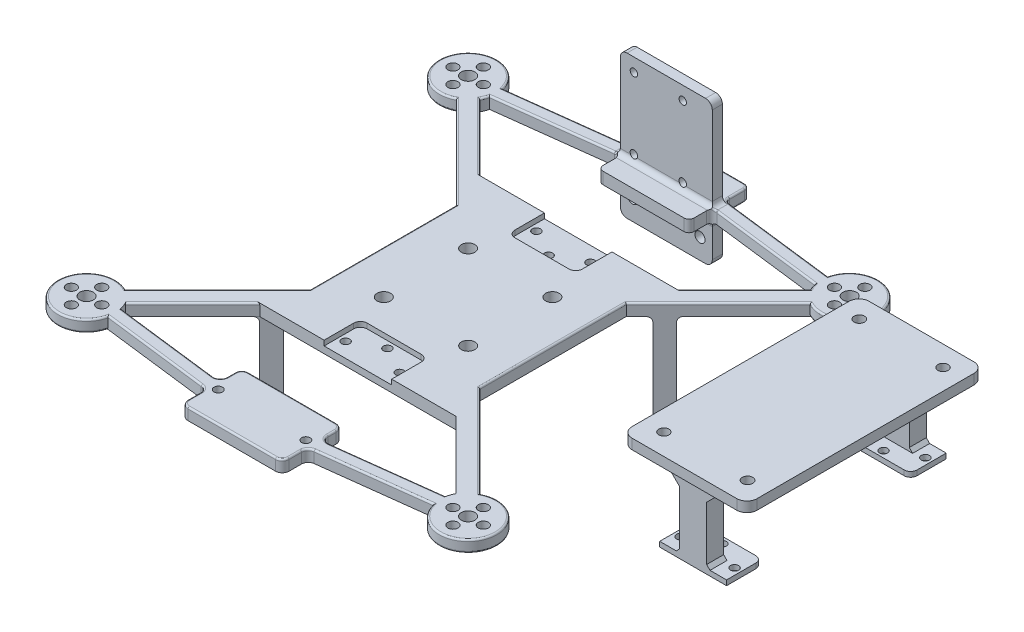
SolidWorks part; units mm, degrees
ref_plane "Front Plane" through (0, 0, 0) normal (0, 0, 1) x (1, 0, 0)
ref_plane "Top Plane" through (0, 0, 0) normal (0, 1, 0) x (1, 0, 0)
ref_plane "Right Plane" through (0, 0, 0) normal (1, 0, 0) x (0, 0, -1)
sketch "Sketch1" plane through (0, 0, 0) normal (0, 1, 0) x (1, 0, 0)
  line L10 (25.2228, 21.7178) -> (52.5194, 49.0143)
  line L11 (29.1718, 32.6991) -> (49.0032, 52.5305)
  line L14 (25.2228, -21.7245) -> (52.5163, -49.018)
  line L15 (29.1386, -32.6991) -> (48.9964, -52.5569)
  line L19 (-25.2228, 21.7178) -> (-52.5879, 49.0829)
  line L20 (-29.1386, -32.6991) -> (-49.0885, -52.649)
  line L22 (-25.2228, -21.7245) -> (-52.6084, -49.1101)
  line L33 (-25.2228, -21.7245) -> (-25.2228, 21.7178)
  line L34 (-16.8093, -62.3977) -> (-48.3224, -58.53)
  line L37 (-8.5504, -52.1195) -> (8.5504, -52.1195)
  line L41 (-17.2966, -58.4661) -> (-48.3352, -54.6566)
  line L42 (25.2228, -21.7245) -> (25.2228, 21.7178)
  line L43 (-48.2996, 54.661) -> (-15.2357, 58.719)
  line L44 (17.1959, -58.4785) -> (48.2122, -54.6717)
  line L45 (16.7086, -62.4101) -> (48.2307, -58.5412)
  line L46 (-29.1718, 32.6991) -> (29.1718, 32.6991)
  line L47 (-29.1386, -32.6991) -> (29.1386, -32.6991)
  line L48 (14.7695, 62.6481) -> (48.2209, 58.5424)
  line L49 (15.135, 58.7314) -> (48.2038, 54.6727)
  line L50 (-13.553, 57.2302) -> (-13.553, 53.6195)
  line L51 (-13.553, 64.1245) -> (-13.553, 68.595)
  line L52 (13.4522, 57.2426) -> (13.4522, 53.6195)
  line L53 (-12.053, 52.1195) -> (11.9522, 52.1195)
  line L54 (-15.053, -56.481) -> (-15.053, -54.1195)
  line L55 (-49.0752, 52.6025) -> (-29.1718, 32.6991)
  line L56 (14.9522, -64.3952) -> (14.9522, -68.095)
  line L57 (-14.8702, 62.6357) -> (-48.3224, 58.53)
  line L58 (12.9522, -70.095) -> (-13.053, -70.095)
  line L64 (-12.053, 70.095) -> (11.9522, 70.095)
  line L65 (13.4522, 68.595) -> (13.4522, 64.1369)
  line L66 (-15.053, -68.095) -> (-15.053, -64.3828)
  line L67 (14.9522, -56.4934) -> (14.9522, -54.1195)
  line L68 (12.9522, -52.1195) -> (-13.053, -52.1195)
  line L69 (14.9522, -52.1195) -> (14.9522, -58.7538)
  arc A0 (-52.6084, -49.1101) -> (-48.3224, -58.53) centre (-56.6207, -56.6207) ccw
  arc A1 (52.5194, 49.0143) -> (48.2209, 58.5424) centre (56.5594, 56.5706) ccw
  arc A2 (-49.0752, 52.6025) -> (-48.2996, 54.661) centre (-56.6207, 56.6207) ccw
  arc A3 (48.9964, -52.5569) -> (48.2122, -54.6717) centre (56.5667, -56.5667) ccw
  arc A8 (-48.3352, -54.6566) -> (-49.0885, -52.649) centre (-56.6207, -56.6207) ccw
  arc A9 (48.2307, -58.5412) -> (52.5163, -49.018) centre (56.5667, -56.5667) ccw
  arc A11 (13.4522, 64.1369) -> (14.7695, 62.6481) centre (14.9522, 64.1369) ccw
  arc A12 (15.135, 58.7314) -> (13.4522, 57.2426) centre (14.9522, 57.2426) ccw
  arc A13 (-13.553, 64.1245) -> (-14.8702, 62.6357) centre (-15.053, 64.1245) cw
  arc A14 (-49.0752, 52.6025) -> (-48.2996, 54.661) centre (-56.6207, 56.6207) ccw
  arc A15 (48.2038, 54.6727) -> (49.0032, 52.5305) centre (56.5594, 56.5706) ccw
  arc A16 (-48.2888, 58.5341) -> (-52.5879, 49.0829) centre (-56.6207, 56.6207) ccw
  arc A17 (14.9522, -56.4934) -> (17.1959, -58.4785) centre (16.9522, -56.4934) ccw
  arc A20 (16.7086, -62.4101) -> (14.9522, -64.3952) centre (16.9522, -64.3952) ccw
  arc A21 (-15.2357, 58.719) -> (-13.553, 57.2302) centre (-15.053, 57.2302) cw
  arc A22 (-13.553, 53.6195) -> (-12.053, 52.1195) centre (-12.053, 53.6195) ccw
  arc A23 (11.9522, 52.1195) -> (13.4522, 53.6195) centre (11.9522, 53.6195) ccw
  arc A24 (11.9522, 70.095) -> (13.4522, 68.595) centre (11.9522, 68.595) cw
  arc A25 (-12.053, 70.095) -> (-13.553, 68.595) centre (-12.053, 68.595) ccw
  arc A26 (-15.053, -56.481) -> (-17.2966, -58.4661) centre (-17.053, -56.481) cw
  arc A27 (-15.053, -64.3828) -> (-16.8093, -62.3977) centre (-17.053, -64.3828) ccw
  arc A28 (-13.053, -70.095) -> (-15.053, -68.095) centre (-13.053, -68.095) cw
  arc A29 (12.9522, -70.095) -> (14.9522, -68.095) centre (12.9522, -68.095) ccw
  arc A30 (14.9522, -54.1195) -> (12.9522, -52.1195) centre (12.9522, -54.1195) ccw
  arc A31 (-15.053, -54.1195) -> (-13.053, -52.1195) centre (-13.053, -54.1195) cw
  point P10 (0, 0)
  point P34 (14.9522, -62.6256)
  point P37 (-15.053, -58.7415)
  point P44 (-28.9553, -58.9711)
  point P57 (13.4522, 58.9379)
  dimension "D1" = 2
  dimension "D2" = 1.5
extrude "Boss-Extrude1" add sketch "Sketch1" along normal blind 3.5 contours A16 L19 L33 L22 A0 L34 L45 A9 L14 L42 L10 A1 L48 L50 L57 L49 A15 L11 L46 L55 A2 L43 A13 L41 A8 L20 L47 L15 A3 L44 L37 region at (0.0088, 0, 0.3906)
sketch "Sketch2" plane through (0, 3.5, 0) normal (0, 1, 0) x (1, 0, 0)
  circle A0 centre (-56.6207, 56.6207) radius 2.003
  circle A1 centre (56.6207, 56.6207) radius 2.003
  circle A2 centre (56.6207, -56.6274) radius 2.003
  circle A3 centre (-56.6207, -56.6274) radius 2.003
  circle A6 centre (56.6207, 61.1356) radius 1.498
  circle A7 centre (61.1356, 56.6207) radius 1.495
  circle A8 centre (56.6207, 52.1058) radius 1.5029
  circle A9 centre (52.1058, 56.6207) radius 1.5021
  circle A10 centre (-56.6207, 61.1356) radius 1.498
  circle A11 centre (-52.1058, 56.6207) radius 1.5021
  circle A12 centre (-56.6207, 52.1058) radius 1.5029
  circle A13 centre (-61.1356, 56.6207) radius 1.495
  circle A14 centre (56.6207, -61.1356) radius 1.498
  circle A15 centre (52.1058, -56.6207) radius 1.5021
  circle A16 centre (56.6207, -52.1058) radius 1.5029
  circle A17 centre (61.1356, -56.6207) radius 1.495
  circle A18 centre (-56.6207, -61.1356) radius 1.498
  circle A19 centre (-52.1058, -56.6207) radius 1.5021
  circle A20 centre (-61.1356, -56.6207) radius 1.495
  circle A21 centre (-56.6207, -52.1058) radius 1.5029
  circle A22 centre (-12.2493, 12.2453) radius 1.9968
  circle A23 centre (-12.2493, -12.7715) radius 1.9976
  circle A24 centre (12.7793, -12.7715) radius 1.9993
  circle A25 centre (12.7793, 12.2453) radius 2.0015
extrude "Cut-Extrude1" cut sketch "Sketch2" against normal through all
sketch "Sketch3" plane through (0, 0, 0) normal (0, -1, 0) x (1, 0, 0)
  line L1 (-25.2228, -21.7178) -> (-52.5879, -49.0829) construction
  line L3 (-29.1718, -32.6991) -> (-32.6879, -29.1829)
  line L4 (-29.1718, -32.6991) -> (-25.6556, -29.1829)
  line L5 (-32.6879, -29.1829) -> (-29.1718, -25.6667)
  line L6 (-25.6556, -29.1829) -> (-29.1718, -25.6667)
  line L7 (32.6879, -29.1829) -> (29.1718, -25.6667)
  line L8 (29.1718, -32.6991) -> (32.6879, -29.1829)
  line L9 (29.1718, -32.6991) -> (25.6556, -29.1829)
  line L10 (25.6556, -29.1829) -> (29.1718, -25.6667)
  line L13 (32.6879, 29.1896) -> (29.1718, 25.6735)
  line L14 (29.1718, 32.7058) -> (32.6879, 29.1896)
  line L15 (25.6556, 29.1896) -> (29.1718, 25.6735)
  line L16 (29.1718, 32.7058) -> (25.6556, 29.1896)
  line L17 (-32.6879, 29.1896) -> (-29.1718, 25.6735)
  line L18 (-29.1718, 32.7058) -> (-25.6556, 29.1896)
  line L19 (-29.1718, 32.7058) -> (-32.6879, 29.1896)
  line L20 (-25.6556, 29.1896) -> (-29.1718, 25.6735)
extrude "Boss-Extrude2" add sketch "Sketch3" along normal blind 30 and the other way blind 2.5
fillet "Fillet1" radius 1.5 8 edges at (30.9299, 0, -30.941) (-27.4137, 0, 27.4316) (30.9299, 0, 30.9477) (-27.4137, 0, -27.4248) (-30.9299, 0, 30.9477) (27.4137, 0, 27.4316) (-30.9299, 0, -30.941) (27.4137, 0, -27.4248)
sketch "Sketch4" plane through (0, 3.5, 0) normal (0, 1, 0) x (1, 0, 0)
  line L8 (-13.885, 59.0576) -> (13.4118, 59.0576)
  line L9 (-13.885, 59.0576) -> (-13.885, 62.0613)
  line L10 (-13.885, 62.0613) -> (13.4118, 62.0613)
  line L11 (13.4118, 59.0576) -> (13.4118, 62.0613)
extrude "Boss-Extrude3" add sketch "Sketch4" along normal blind 27 and the other way blind 15.5
fillet "Fillet2" radius 1.5 6 edges at (-0.2366, 0, -59.0576) (13.4118, 3.5, -60.5595) (-0.2366, 3.5, -59.0576) (-13.885, 3.5, -60.5595) (-13.885, 0, -60.5595) (13.4118, 0, -60.5595)
fillet "Fillet3" radius 2 4 edges at (13.4118, -12, -60.5595) (-13.885, -12, -60.5595) (13.4118, 30.5, -60.5595) (-13.885, 30.5, -60.5595)
sketch "Sketch5" plane through (0, 0, -62.0613) normal (0, 0, -1) x (-1, 0, 0)
  circle A3 centre (9.8595, 5.5028) radius 1.1031
  circle A4 centre (-4.6441, 5.5028) radius 1.0992
  circle A5 centre (9.8595, 26.5151) radius 1.0963
  circle A6 centre (-4.6441, 26.5151) radius 1.0933
  circle A7 centre (-9.7641, -6) radius 1.4993
  circle A8 centre (10.2386, -6) radius 1.4966
extrude "Cut-Extrude2" cut sketch "Sketch5" against normal up to next
fillet "Fillet6" radius 0.5 61 edges at (-14.7161, 3.6574, -58.6919) (-15.3102, 3.5019, -58.7099) (14.5178, 3.5527, -58.6783) (15.0236, 3.5, -58.7409) (32.7041, 3.5, 56.5751) (-0.0504, 3.5, 52.1195) (32.4696, 3.5, 60.4757) (-31.5795, 0, -60.5849) (-13.9296, 0, -63.1306) (-13.553, 0, -66.3598) (-13.1136, 0, -69.6557) (31.4952, 0, -60.5953) (13.8288, 0, -63.1429) (13.4522, 0, -66.366) (13.0129, 0, -69.6557) (-31.5795, 3.5, -60.5849) (-13.9296, 3.5, -63.1306) (-13.553, 3.5, -66.3598) (-13.1136, 3.5, -69.6557) (-0.0504, 3.5, -70.095) (13.0129, 3.5, -69.6557) (13.4522, 3.5, -66.366) (13.8288, 3.5, -63.1429) (-31.8423, 3.5, -56.6808) (-48.6209, 3.5, -53.6067) (31.6694, 3.5, -56.7021) (48.5317, 3.5, -53.5748) (39.0875, 3.5, -42.6148) (-39.1235, 3.5, -42.6508) (38.8711, 3.5, -35.366) (25.2228, 3.5, 0.0034) (38.8696, 3.5, 35.3713) (64.3788, 0, 60.0823) (64.3788, 3.5, 60.0823) (-39.1136, 3.5, 42.674) (-32.8159, 3.5, 56.5614) (-32.5659, 3.5, 60.4638) (-64.3713, 0, 60.1472) (-64.3713, 3.5, 60.1472) (-38.9156, 3.5, 35.4173) (-25.2228, 3.5, 0.0034) (-38.9054, 3.5, -35.4003) (-64.4022, 3.5, -60.1603) (-64.4022, 0, -60.1603) (64.3699, 0, -60.0942) (-0.0504, 0, -70.095) (31.4952, 3.5, -60.5953) (64.3699, 3.5, -60.0942) (15.627, 3.5, 57.9912) (14.9522, 3.5, 55.3064) (14.3664, 3.5, 52.7053) (-14.4672, 3.5, 52.7053) (-15.053, 3.5, 55.3003) (-15.7277, 3.5, 57.9789) (15.4544, 3.5, 63.0699) (14.9522, 3.5, 66.2451) (14.3664, 3.5, 69.5092) (-0.0504, 3.5, 70.095) (-14.4672, 3.5, 69.5092) (-15.053, 3.5, 66.2389) (-15.5551, 3.5, 63.0575)
sketch "Sketch6" plane through (0, 3.5, 0) normal (0, 1, 0) x (1, 0, 0)
  line L4 (10.0048, -23.9249) -> (10.0048, -32.6991)
  line L5 (-29.8789, 32.6991) -> (29.8789, 32.6991) construction
  line L6 (10.0048, -32.6991) -> (-10.0395, -32.6991)
  line L7 (-10.0395, -32.6991) -> (-10.0395, -23.9249)
  line L8 (-8.0395, -21.9249) -> (8.0048, -21.9249)
  line L10 (-8.0395, 21.9249) -> (8.0048, 21.9249)
  line L11 (10.0048, 23.9249) -> (10.0048, 32.6991)
  line L12 (10.0048, 32.6991) -> (-10.0395, 32.6991)
  line L13 (-10.0395, 32.6991) -> (-10.0395, 23.9249)
  arc A0 (8.0048, 21.9249) -> (10.0048, 23.9249) centre (8.0048, 23.9249) ccw
  arc A1 (-10.0395, 23.9249) -> (-8.0395, 21.9249) centre (-8.0395, 23.9249) ccw
  arc A2 (8.0048, -21.9249) -> (10.0048, -23.9249) centre (8.0048, -23.9249) cw
  arc A3 (-10.0395, -23.9249) -> (-8.0395, -21.9249) centre (-8.0395, -23.9249) cw
  dimension "D1" = 2
extrude "Cut-Extrude3" cut sketch "Sketch6" against normal blind 1.5
sketch "Sketch7" plane through (0, 2, 0) normal (0, 1, 0) x (1, 0, 0)
  circle A0 centre (-8.0479, 28.312) radius 1.205
  circle A1 centre (-0.0173, 23.9294) radius 1.1998
  circle A2 centre (8.0011, 28.312) radius 1.205
  circle A3 centre (8.0011, -28.312) radius 1.205
  circle A4 centre (-0.0173, -23.9294) radius 1.1998
  circle A5 centre (-8.0479, -28.312) radius 1.205
extrude "Cut-Extrude5" cut sketch "Sketch7" against normal through all
sketch "Sketch10" plane through (0, 3.5, 0) normal (0, 1, 0) x (1, 0, 0)
  circle A0 centre (-13.053, -61.1073) radius 1.2524
  circle A1 centre (12.9522, -61.1073) radius 1.2475
extrude "Cut-Extrude6" cut sketch "Sketch10" against normal through all
sketch "Sketch11" plane through (0, 0, 0) normal (0, 1, 0) x (1, 0, 0)
  line L4 (89.4618, 32.5991) -> (89.4618, 23.9249)
  line L5 (107.4062, 22.0249) -> (91.3618, 22.0249)
  line L6 (109.3062, 32.5991) -> (109.3062, 23.9249)
  line L7 (89.4618, 32.5991) -> (109.3062, 32.5991)
  line L10 (109.3062, -32.5991) -> (109.3062, -23.9249)
  line L11 (107.4062, -22.0249) -> (91.3618, -22.0249)
  line L12 (89.4618, -32.5991) -> (109.3062, -32.5991)
  line L13 (89.4618, -32.5991) -> (89.4618, -23.9249)
  arc A2 (91.3618, 22.0249) -> (89.4618, 23.9249) centre (91.3618, 23.9249) cw
  arc A3 (107.4062, 22.0249) -> (109.3062, 23.9249) centre (107.4062, 23.9249) ccw
  arc A4 (107.4062, -22.0249) -> (109.3062, -23.9249) centre (107.4062, -23.9249) cw
  arc A5 (91.3618, -22.0249) -> (89.4618, -23.9249) centre (91.3618, -23.9249) ccw
extrude "Boss-Extrude4" add sketch "Sketch11" along normal blind 1.5 separate body
sketch "Sketch12" plane through (0, 1.5, 0) normal (0, 1, 0) x (1, 0, 0)
  circle A0 centre (91.3535, 28.3053) radius 1.205
  circle A1 centre (99.384, 23.9228) radius 1.1998
  circle A2 centre (107.4025, 28.3053) radius 1.205
  circle A3 centre (107.4025, -28.3186) radius 1.205
  circle A4 centre (99.384, -23.9361) radius 1.1998
  circle A5 centre (91.3535, -28.3186) radius 1.205
extrude "Cut-Extrude7" cut sketch "Sketch12" against normal through all
sketch "Sketch13" plane through (0, 1.5, 0) normal (0, 1, 0) x (1, 0, 0)
  line L2 (109.3062, 32.5991) -> (89.4618, 32.5991) construction
  line L7 (95.3874, 32.5991) -> (95.3874, 27.5424)
  line L8 (95.3874, 27.5424) -> (103.3936, 27.5424)
  line L9 (103.3936, 32.5991) -> (103.3936, 27.5424)
  line L15 (103.3936, -32.5991) -> (103.3936, -27.5424)
  line L16 (95.3874, -32.5991) -> (95.3874, -27.5424)
  line L17 (95.3874, -27.5424) -> (103.3936, -27.5424)
  line L18 (95.3874, -32.5991) -> (103.3936, -32.5991)
  line L19 (95.3874, 32.5991) -> (103.3936, 32.5991)
extrude "Boss-Extrude5" add sketch "Sketch13" along normal blind 23.5 and the other way blind 1.253
sketch "Sketch14" plane through (0, 25, 0) normal (0, 1, 0) x (1, 0, 0)
  line L0 (80.8723, 35.1637) -> (80.8723, -35.1882)
  line L3 (80.8723, 35.1637) -> (117.9365, 35.1637)
  line L4 (80.8723, -35.1882) -> (117.9365, -35.1882)
  line L5 (117.9365, -35.1882) -> (117.9365, 35.1637)
extrude "Boss-Extrude6" add sketch "Sketch14" along normal blind 1.5 and the other way blind 1.5
fillet "Fillet10" radius 3 4 edges at (80.8723, 25, -35.1637) (117.9365, 25, -35.1637) (80.8723, 25, 35.1882) (117.9365, 25, 35.1882)
sketch "Sketch15" plane through (0, 26.5, 0) normal (0, 1, 0) x (1, 0, 0)
  circle A4 centre (86.9844, 29.1301) radius 1.546
  circle A5 centre (111.8244, 29.1301) radius 1.5226
  circle A6 centre (86.9844, -28.8874) radius 1.5055
  circle A7 centre (111.8244, -28.8874) radius 1.5537
extrude "Cut-Extrude8" cut sketch "Sketch15" against normal up to next (3 mm away)
chamfer "Chamfer2" distance 1 angle 45 4 edges at (95.3874, 1.5, 30.0707) (95.3874, 1.5, -30.0707) (103.3936, 1.5, -30.0707) (103.3936, 1.5, 30.0707)
chamfer "Chamfer3" distance 5 angle 45 4 edges at (103.3936, 23.5, 30.0707) (95.3874, 23.5, 30.0707) (95.3874, 23.5, -30.0707) (103.3936, 23.5, -30.0707)
